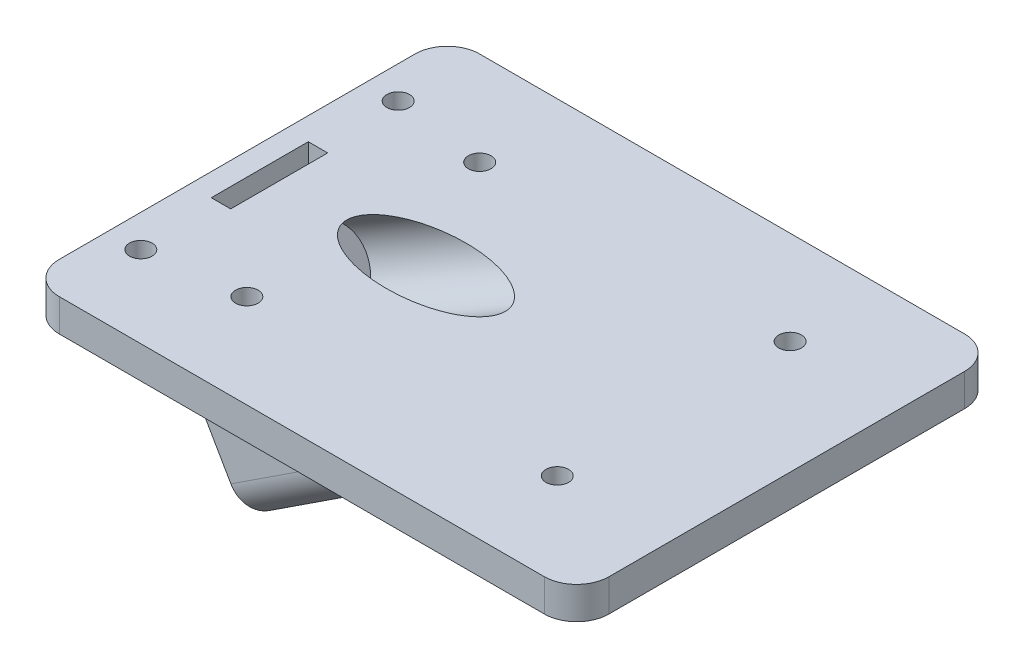
SolidWorks part; units mm, degrees
ref_plane "Ebene vorne" through (0, 0, 0) normal (0, 0, 1) x (1, 0, 0)
ref_plane "Ebene oben" through (0, 0, 0) normal (0, 1, 0) x (1, 0, 0)
ref_plane "Ebene rechts" through (0, 0, 0) normal (1, 0, 0) x (0, 0, -1)
sketch "Skizze2" plane through (0, 0, 0) normal (0, 1, 0) x (1, 0, 0)
  line L0 (-32.5, 32.5) -> (-32.5, -32.5) construction
  line L1 (42.5, 32.5) -> (-42.5, 32.5)
  line L2 (42.5, 32.5) -> (42.5, -32.5)
  line L3 (42.5, -32.5) -> (-42.5, -32.5)
  line L4 (-42.5, 32.5) -> (-42.5, -32.5)
  line L5 (42.5, 32.5) -> (-42.5, -32.5) construction
  line L6 (42.5, -32.5) -> (-42.5, 32.5) construction
  point P0 (0, 0)
  dimension "D1" = 65
  dimension "D2" = 85
  dimension "D3" = 10
extrude "Aufsatz-Linear austragen1" add sketch "Skizze2" along normal blind 5
sketch "Skizze3" plane through (0, 5, 0) normal (0, 1, 0) x (1, 0, 0)
  line L0 (-42.5, -32.5) -> (42.5, -32.5) construction
  line L1 (-42.5, 32.5) -> (-32.5, 32.5)
  line L2 (-42.5, 32.5) -> (-42.5, -32.5)
  line L3 (-42.5, -32.5) -> (-32.5, -32.5)
  line L4 (-32.5, 32.5) -> (-32.5, -32.5)
  dimension "D1" = 10
extrude "Aufsatz-Linear austragen2" add sketch "Skizze3" along normal blind 10
sketch "Skizze4" plane through (0, 0, 0) normal (0, 0, 1) x (1, 0, 0)
  line L0 (17.769, 0) -> (-25.9637, -28.6417)
  line L1 (-42.5, 0) -> (42.5, 0) construction
  line L2 (-25.9637, -28.6417) -> (-42.5, 0)
  line L9 (-42.5, 0) -> (42.5, 0)
  line L10 (42.5, 0) -> (42.5, 5)
  line L11 (42.5, 5) -> (-32.5, 5)
  line L12 (-32.5, 5) -> (-32.5, 15)
  line L13 (-32.5, 15) -> (-42.5, 15)
  line L14 (-42.5, 15) -> (-42.5, 0)
  line L15 (17.769, 0) -> (42.5, 0)
  line L16 (42.5, 0) -> (42.5, 5)
  line L17 (42.5, 5) -> (-32.5, 5)
  line L18 (-32.5, 5) -> (-32.5, 15)
  line L19 (-32.5, 15) -> (-42.5, 15)
  line L20 (-42.5, 15) -> (-42.5, 0)
  dimension "D1" = 60
  dimension "D2" = 0
extrude "Aufsatz-Linear austragen3" add sketch "Skizze4" along normal blind 15 and the other way blind 15
hole_wizard "Durchgangsloch für M61" positions "Skizze5" profile "Skizze6" hole size "M6" standard "DIN" end condition through all
sketch "Skizze5" plane through (-31.875, -18.403, 0) normal (-0.866, -0.5, 0) x (0, 0, 1)
  point P0 (0, 10.9797)
sketch "Skizze6" plane through (-37.3648, -8.8944, 0) normal (0, 0, 1) x (0.5, -0.866, 0)
  line L0 (0, 0) -> (0, 81.1122)
  line L1 (0, 81.1122) -> (3.3, 81.1122)
  line L2 (3.3, 81.1122) -> (3.3, 0)
  line L5 (3.3, 0) -> (0, 0)
  line L11 (0, -6.35) -> (0, 107.95) construction
  dimension "Bohrerdurchmesser" = 6.6
  dimension "Bohrungstiefe" = 81.1122
ref_plane "Ebene1" through (2.766, 1.597, 0) normal (-0.866, -0.5, 0) x (0, 0, 1)
sketch "Skizze7" plane through (2.766, 1.597, 0) normal (-0.866, -0.5, 0) x (0, 0, 1)
  circle A0 centre (0, 10.9797) radius 6.1263
extrude "Schnitt-Linear austragen1" cut sketch "Skizze7" along normal blind 30
sketch "Skizze8" plane through (-31.875, -18.403, 0) normal (-0.866, -0.5, 0) x (0, 0, 1)
  line L1 (-3, -7.953) -> (3, -7.953)
  line L2 (-3, -7.953) -> (-3, 2.047)
  line L3 (-3, 2.047) -> (3, 2.047)
  line L4 (3, -7.953) -> (3, 2.047)
  line L5 (-3, -7.953) -> (3, 2.047) construction
  line L6 (-3, 2.047) -> (3, -7.953) construction
  point P0 (0, -2.953)
  dimension "D1" = 10
  dimension "D2" = 6
extrude "Aufsatz-Linear austragen4" add sketch "Skizze8" along normal blind 3
fillet "Verrundung1" radius 2 2 edges at (-32.8985, -16.6303, 0) (-27.8985, -25.2906, 0)
fillet "Verrundung2" radius 10 2 edges at (-12.3655, 0, -15) (-12.3655, 0, 15)
fillet "Verrundung3" radius 5 4 edges at (-42.5, 7.5, -32.5) (-42.5, 7.5, 32.5) (42.5, 2.5, -32.5) (42.5, 2.5, 32.5)
fillet "Verrundung4" radius 5 4 edges at (13.2969, -2.9289, 17.9289) (13.2969, -2.9289, -17.9289) (-11.7318, -19.3209, 15) (-11.7318, -19.3209, -15)
sketch "Skizze9" plane through (0, 5, 0) normal (0, 1, 0) x (1, 0, 0)
  line L0 (1, -45.3373) -> (1, 49954.6627) construction
  line L1 (-32.5, -32.5) -> (-32.5, 32.5) construction
  line L2 (20.1281, 0) -> (-49979.8719, 0) construction
  line L3 (42.5, -27.5) -> (42.5, 27.5) construction
  line L4 (-37.5, 9.2268) -> (-37.5, 50009.2268) construction
  line L5 (-42.5, 27.5) -> (-42.5, -27.5) construction
  circle A0 centre (-23, 18) radius 1.75
  circle A1 centre (25, 18) radius 1.75
  circle A2 centre (-23, -18) radius 1.75
  circle A3 centre (25, -18) radius 1.75
  circle A4 centre (-37.5, 19.9) radius 1.75
  circle A5 centre (-37.5, -19.9) radius 1.75
  point P8 (42.5, 0)
  dimension "D2" = 3.5
  dimension "D6" = 3.5
  dimension "D1" = 33.5
  dimension "D3" = 48
  dimension "D4" = 36
  dimension "D5" = 5
  dimension "D7" = 39.8
extrude "Schnitt-Linear austragen2" cut sketch "Skizze9" against normal through all and the other way through all
sketch "Skizze11" plane through (0, 15, 0) normal (0, 1, 0) x (1, 0, 0)
  circle A0 centre (-37.5, -19.9) radius 1.75 construction
  circle A1 centre (-37.5, 19.9) radius 1.75 construction
  circle A2 centre (-37.5, -19.9) radius 1.75
  circle A3 centre (-37.5, 19.9) radius 1.75
  circle A4 centre (-37.5, 19.9) radius 2.575
  circle A5 centre (-37.5, -19.9) radius 2.575
  dimension "D1" = 5.15
  dimension "D2" = 5.15
extrude "Schnitt-Linear austragen4" cut sketch "Skizze11" against normal blind 3
sketch "Skizze10" plane through (0, 0, 0) normal (0, -1, 0) x (1, 0, 0)
  circle A0 centre (25, 18) radius 1.75 construction
  circle A1 centre (25, -18) radius 1.75 construction
  circle A2 centre (-23, -18) radius 1.75 construction
  circle A3 centre (-23, 18) radius 1.75 construction
  circle A4 centre (25, 18) radius 1.75 construction
  circle A5 centre (25, -18) radius 1.75 construction
  circle A6 centre (-23, -18) radius 1.75 construction
  circle A7 centre (-23, 18) radius 1.75 construction
  circle A8 centre (25, 18) radius 3
  circle A9 centre (25, -18) radius 3
  circle A10 centre (-23, -18) radius 3
  circle A11 centre (-23, 18) radius 3
  circle A12 centre (-37.5, -19.9) radius 1.75 construction
  circle A13 centre (-37.5, 19.9) radius 1.75 construction
  circle A14 centre (-37.5, -19.9) radius 1.75 construction
  circle A15 centre (-37.5, 19.9) radius 1.75 construction
  circle A16 centre (-37.5, 19.9) radius 3
  circle A17 centre (-37.5, -19.9) radius 3
  dimension "D1" = 6
  dimension "D2" = 6
  dimension "D3" = 6
  dimension "D4" = 6
  dimension "D5" = 6
  dimension "D6" = 6
extrude "Schnitt-Linear austragen3" cut sketch "Skizze10" against normal blind 1 and the other way through all
sketch "Skizze12" plane through (0, 5, 0) normal (0, 1, 0) x (1, 0, 0)
  line L0 (-32.5, -32.5) -> (37.5, -32.5) construction
  line L1 (-15.5725, -32.5) -> (-72.4361, -32.5)
  line L2 (-15.5725, -32.5) -> (-15.5725, 34.9017)
  line L3 (-15.5725, 34.9017) -> (-72.4361, 34.9017)
  line L4 (-72.4361, -32.5) -> (-72.4361, 34.9017)
extrude "Schnitt-Linear austragen5" cut sketch "Skizze12" along normal through all
sketch "Skizze13" plane through (0, 5, 0) normal (0, 1, 0) x (1, 0, 0)
  line L0 (-37.5, -19.9) -> (-37.5, 49980.1) construction
  line L1 (-37.5, 0) -> (-30.059, 0) construction
  line L3 (-39, -7.5) -> (-36, -7.5)
  line L4 (-39, -7.5) -> (-39, 7.5)
  line L5 (-39, 7.5) -> (-36, 7.5)
  line L6 (-36, -7.5) -> (-36, 7.5)
  line L7 (-39, -7.5) -> (-36, 7.5) construction
  line L8 (-39, 7.5) -> (-36, -7.5) construction
  point P5 (-37.5, 0)
  point P7 (-37.5, 24980.1)
  dimension "D1" = 15
  dimension "D2" = 3
extrude "Schnitt-Linear austragen6" cut sketch "Skizze13" against normal blind 3
